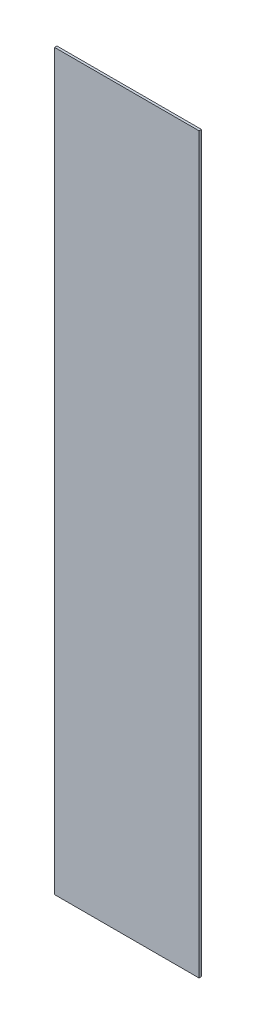
SolidWorks part; units mm, degrees
ref_plane "Front Plane" through (0, 0, 0) normal (0, 0, 1) x (1, 0, 0)
ref_plane "Top Plane" through (0, 0, 0) normal (0, 1, 0) x (1, 0, 0)
ref_plane "Right Plane" through (0, 0, 0) normal (1, 0, 0) x (0, 0, -1)
sketch "Sketch1" plane through (0, 0, 0) normal (0, 0, 1) x (1, 0, 0)
  line L1 (-60, 304.8) -> (60, 304.8)
  line L2 (-60, 304.8) -> (-60, -304.8)
  line L3 (-60, -304.8) -> (60, -304.8)
  line L4 (60, 304.8) -> (60, -304.8)
  line L5 (-60, 304.8) -> (60, -304.8) construction
  line L6 (-60, -304.8) -> (60, 304.8) construction
  point P0 (0, 0)
  point P5 (0, 0)
  dimension "D1" = 609.6
  dimension "D2" = 120
extrude "Boss-Extrude1" add sketch "Sketch1" along normal blind 2
